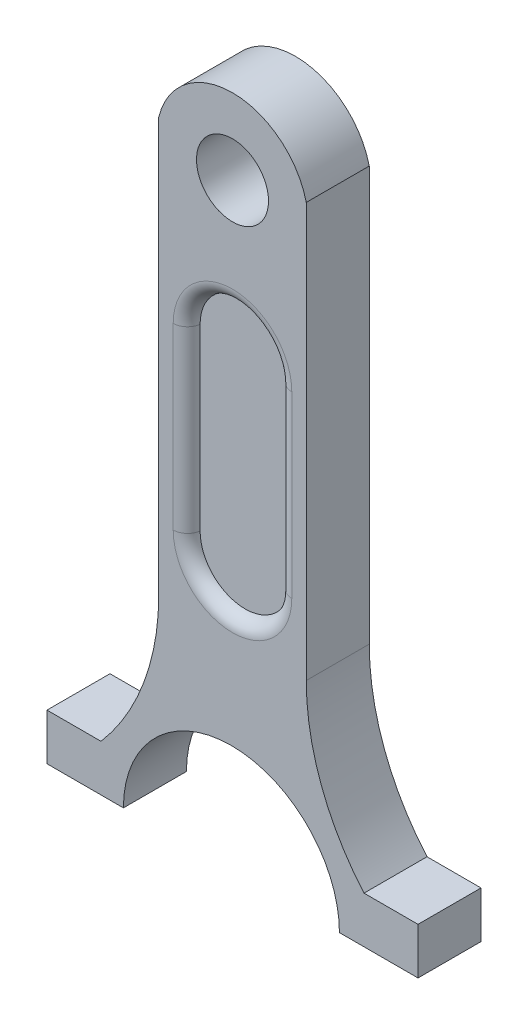
SolidWorks part; units mm, degrees
ref_plane "Front Plane" through (0, 0, 0) normal (0, 0, 1) x (1, 0, 0)
ref_plane "Top Plane" through (0, 0, 0) normal (0, 1, 0) x (1, 0, 0)
ref_plane "Right Plane" through (0, 0, 0) normal (1, 0, 0) x (0, 0, -1)
sketch "Sketch2" plane through (0, 0, 0) normal (0, 0, 1) x (1, 0, 0)
  line L0 (0, 34.6258) -> (0, 21.9492) construction
  line L1 (-10.4068, -8.2026) -> (-10.4068, -66.6226)
  line L3 (-18.5558, -88.5293) -> (-18.5558, -95.0894)
  line L4 (10.4068, -8.2026) -> (10.4068, -66.6226)
  line L5 (-10.4068, -66.6226) -> (-10.4068, -95.0894) construction
  line L6 (-18.5558, -95.0894) -> (18.5558, -95.0894)
  line L7 (18.5558, -88.5293) -> (18.5558, -95.0894)
  arc A0 (-10.4068, -8.2026) -> (10.4068, -8.2026) centre (0, -10.7029) cw
  arc A1 (-10.4068, -66.6226) -> (-18.5558, -88.5293) centre (-43.9268, -66.6226) cw
  arc A2 (10.4068, -66.6226) -> (18.5558, -88.5293) centre (43.9268, -66.6226) ccw
  circle A3 centre (0, -10.7029) radius 5.08
  point P14 (0, -95.0894)
  dimension "D3" = 10.16
  dimension "D1" = 58.42
  dimension "D2" = 28.4668
  dimension "D4" = 95.0894
extrude "Boss-Extrude1" add sketch "Sketch2" along normal blind 8.89
sketch "Sketch3" plane through (0, 0, 8.89) normal (0, 0, 1) x (1, 0, 0)
  line L0 (18.5558, -95.0894) -> (15.0877, -95.0894) construction
  line L1 (-18.5558, -95.0894) -> (-15.3923, -95.0894) construction
  line L2 (-18.5558, -95.0894) -> (18.5558, -95.0894) construction
  line L3 (-15.3923, -95.0894) -> (15.0877, -95.0894)
  arc A0 (-15.3923, -95.0894) -> (15.0877, -95.0894) centre (-0.1523, -95.0894) cw
  point P7 (0, 0)
  dimension "D1" = 15.24
extrude "Cut-Extrude1" cut sketch "Sketch3" against normal blind 8.89
sketch "Sketch8" plane through (0, 0, 8.89) normal (0, 0, 1) x (1, 0, 0)
  line L0 (0, -20.8629) -> (0, -44.9929) construction
  line L1 (0, -44.9929) -> (-35.3928, -44.9929) construction
  line L2 (6.35, -32.3671) -> (-6.35, -32.3671) construction
  line L3 (-6.35, -32.3671) -> (-6.35, -57.6188)
  line L4 (6.35, -32.3671) -> (6.35, -57.6188)
  arc A2 (-6.35, -32.3671) -> (6.35, -32.3671) centre (0, -32.3671) cw
  arc A3 (-6.35, -57.6188) -> (6.35, -57.6188) centre (0, -57.6188) ccw
  point P12 (0, -32.3671)
  point P16 (6.35, -44.9929)
  point P18 (-6.35, -44.9929)
  dimension "D1" = 24.13
  dimension "D2" = 6.35
extrude "Cut-Extrude4" cut sketch "Sketch8" against normal blind 1.778 contours L4 A3 L3 A2
sketch "Sketch9" plane through (0, 0, 0) normal (0, 0, -1) x (-1, 0, 0)
  line L2 (6.35, -57.6188) -> (6.35, -32.3671)
  line L3 (-6.35, -32.3671) -> (-6.35, -57.6188)
  line L4 (6.35, -57.6188) -> (6.35, -32.3671)
  line L5 (-6.35, -32.3671) -> (-6.35, -57.6188)
  arc A2 (6.35, -32.3671) -> (-6.35, -32.3671) centre (0, -32.3671) ccw
  arc A3 (-6.35, -57.6188) -> (6.35, -57.6188) centre (0, -57.6188) ccw
  arc A4 (6.35, -32.3671) -> (-6.35, -32.3671) centre (0, -32.3671) ccw
  arc A5 (-6.35, -57.6188) -> (6.35, -57.6188) centre (0, -57.6188) ccw
  dimension "D1" = 0
extrude "Cut-Extrude5" cut sketch "Sketch9" against normal blind 1.778 contours A4 L5 A5 L4
sketch "Sketch13" plane through (-18.5558, 0, 0) normal (-1, 0, 0) x (0, 0, 1)
  line L1 (0, -88.5293) -> (8.89, -88.5293)
  line L2 (0, -88.5293) -> (0, -95.0894)
  line L3 (0, -95.0894) -> (8.89, -95.0894)
  line L4 (8.89, -88.5293) -> (8.89, -95.0894)
extrude "Boss-Extrude6" add sketch "Sketch13" along normal blind 7.62
sketch "Sketch14" plane through (18.5558, 0, 0) normal (1, 0, 0) x (0, 0, -1)
  line L1 (-8.89, -88.5293) -> (0, -88.5293)
  line L2 (-8.89, -88.5293) -> (-8.89, -95.0894)
  line L3 (-8.89, -95.0894) -> (0, -95.0894)
  line L4 (0, -88.5293) -> (0, -95.0894)
extrude "Boss-Extrude7" add sketch "Sketch14" along normal blind 7.62
fillet "Fillet1" radius 2.032 8 edges at (0, -63.9688, 0) (-6.35, -44.9929, 0) (6.35, -44.9929, 0) (0, -26.0171, 0) (0, -26.0171, 8.89) (-6.35, -44.9929, 8.89) (0, -63.9688, 8.89) (6.35, -44.9929, 8.89)
sketch "Sketch15" plane through (0, -95.0894, 0) normal (0, -1, 0) x (1, 0, 0)
  line L0 (-20.784, 0) -> (-20.784, 8.89) construction
  line L1 (-0.1523, 8.89) -> (-0.1523, -4.2435) construction
  line L2 (-26.1758, 4.445) -> (-15.3923, 4.445) construction
  line L3 (-26.1758, 0) -> (-26.1758, 8.89) construction
  line L4 (-15.3923, 0) -> (-15.3923, 8.89) construction
  line L5 (-26.1758, 0) -> (-15.3923, 0) construction
  line L6 (-26.1758, 8.89) -> (-15.3923, 8.89) construction
  line L7 (15.0877, 8.89) -> (-15.3923, 8.89) construction
  line L8 (26.1758, 8.89) -> (26.1758, 0) construction
  circle A0 centre (-20.784, 4.445) radius 3.556
  circle A1 centre (20.4794, 4.445) radius 3.556
  dimension "D1" = 7.112
  dimension "D2" = 52.3515
extrude "Cut-Extrude6" cut sketch "Sketch15" against normal blind 3.81
